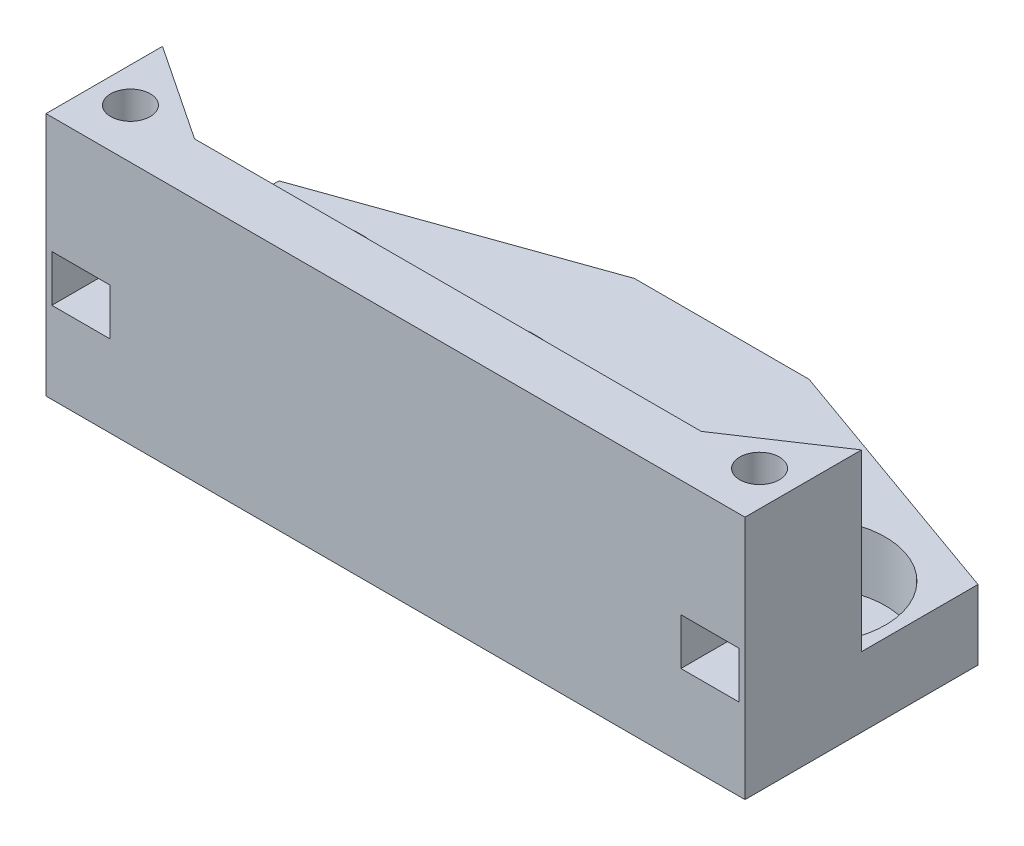
SolidWorks part; units mm, degrees
ref_plane "Front Plane" through (0, 0, 0) normal (0, 0, 1) x (1, 0, 0)
ref_plane "Top Plane" through (0, 0, 0) normal (0, 1, 0) x (1, 0, 0)
ref_plane "Right Plane" through (0, 0, 0) normal (1, 0, 0) x (0, 0, -1)
sketch "Sketch1" plane through (0, 0, 0) normal (0, 1, 0) x (1, 0, 0)
  line L0 (0, 0) -> (60, 0)
  line L1 (60, 0) -> (60, 20)
  line L2 (60, 20) -> (37.5, 28)
  line L3 (37.5, 28) -> (22.5, 28)
  line L4 (22.5, 28) -> (0, 20)
  line L5 (0, 20) -> (0, 0)
  dimension "D1" = 20
  dimension "D2" = 8
  dimension "D3" = 15
  dimension "D4" = 60
extrude "Boss-Extrude1" add sketch "Sketch1" along normal blind 6
sketch "Sketch2" plane through (0, 6, 0) normal (0, 1, 0) x (1, 0, 0)
  line L0 (6.1696, 13) -> (50006.1696, 13) construction
  line L2 (30, 21) -> (30, -49979) construction
  line L3 (37.5, 28) -> (22.5, 28) construction
  line L4 (22.5, 13) -> (37.5, 13)
  line L5 (0, 0) -> (60, 0) construction
  circle A0 centre (7.5, 13) radius 2.15
  circle A1 centre (22.5, 13) radius 2.15
  circle A2 centre (37.5, 13) radius 2.15
  circle A3 centre (52.5, 13) radius 2.15
  circle A4 centre (7.5, 13) radius 6.55
  circle A5 centre (22.5, 13) radius 6.55
  circle A6 centre (37.5, 13) radius 6.55
  circle A7 centre (52.5, 13) radius 6.55
  point P11 (30, 13)
  point P16 (30, 28)
  dimension "D1" = 15
  dimension "D2" = 15
  dimension "D3" = 15
  dimension "D4" = 4.3
  dimension "D6" = 13.1
  dimension "D5" = 13
extrude "Boss-Extrude2" [suppressed] add sketch "Sketch2" along normal blind 25 contours A0 | A1 | A2 | A3
sketch "Sketch3" plane through (0, 6, 0) normal (0, 1, 0) x (1, 0, 0)
  line L0 (0, 0) -> (15, 0)
  line L1 (0, 0) -> (60, 0) construction
  line L2 (15, 0) -> (0, 10)
  line L3 (0, 20) -> (0, 0) construction
  line L4 (0, 10) -> (0, 0)
  line L5 (60, 0) -> (60, 10)
  line L6 (60, 0) -> (60, 20) construction
  line L7 (60, 10) -> (45, 0)
  line L8 (45, 0) -> (60, 0)
  line L9 (8.25, 4.5) -> (51.75, 4.5)
  line L10 (45, 0) -> (15, 0)
  line M13 (0, 20) -> (0, 0)
  line M14 (0, 0) -> (60, 0)
  line M15 (60, 0) -> (60, 20)
  dimension "D1" = 4.5
  dimension "D2" = 10
  dimension "D3" = 15
extrude "Boss-Extrude3" add sketch "Sketch3" along normal blind 15 contours L2 M14 M13 | L9 L2 L7 M14 | L7 M15 M14 region at (5, 6, -3.3333) region at (30, 6, -2.3878) region at (55, 6, -3.3333)
sketch "Sketch4" plane through (0, 21, 0) normal (0, 1, 0) x (1, 0, 0)
  line L0 (60, 0) -> (60, 10) construction
  line L1 (0, 10) -> (0, 0) construction
  line L2 (0, 0) -> (60, 0) construction
  line L3 (22.5, 2.25) -> (37.5, 2.25) construction
  line L4 (30, 28) -> (30, 0) construction
  line L5 (37.5, 28) -> (22.5, 28) construction
  circle A0 centre (3, 4.25) radius 1.7
  circle A1 centre (57, 4.25) radius 1.7
  circle A2 centre (22.5, 2.25) radius 1.7
  circle A3 centre (37.5, 2.25) radius 1.7
  point P19 (30, 2.25)
  dimension "D1" = 3.4
  dimension "D2" = 15
  dimension "D3" = 2
  dimension "D4" = 3
  dimension "D5" = 3
  dimension "D6" = 2.25
extrude "Cut-Extrude1" cut sketch "Sketch4" against normal blind 10 contours A0 | A1 region at (3, 21, -4.25) region at (57, 21, -4.25)
sketch "Sketch6" plane through (0, 21, 0) normal (0, 1, 0) x (1, 0, 0)
  line L0 (5.5, 2.8066) -> (5.5, 0)
  line L1 (5.5, 5.6934) -> (3, 7.1368)
  line L2 (3, 7.1368) -> (0.5, 5.6934)
  line L3 (0.5, 5.6934) -> (0.5, 2.8066)
  line L4 (0.5, 2.8066) -> (3, 1.3632)
  line L5 (3, 1.3632) -> (5.5, 2.8066)
  line L6 (5.5, 2.8066) -> (5.5, 5.6934)
  line L7 (57, 7.1368) -> (54.5, 5.6934)
  line L8 (54.5, 5.6934) -> (54.5, 2.8066)
  line L9 (54.5, 2.8066) -> (57, 1.3632)
  line L10 (57, 1.3632) -> (59.5, 2.8066)
  line L11 (59.5, 2.8066) -> (59.5, 5.6934)
  line L12 (59.5, 5.6934) -> (57, 7.1368)
  line L13 (0, 0) -> (60, 0) construction
  line L14 (0.5, 2.8066) -> (0.5, 0)
  line L15 (0.5, 0) -> (5.5, 0)
  line L16 (59.5, 2.8066) -> (59.5, 0)
  line L17 (59.5, 0) -> (54.5, 0)
  line L18 (54.5, 0) -> (54.5, 2.8066)
  circle A0 centre (3, 4.25) radius 2.5 construction
  circle A1 centre (57, 4.25) radius 2.5 construction
  circle M17 centre (57, 4.25) radius 1.7
  line M18 (0, 0) -> (60, 0)
  dimension "D1" = 5
extrude "Cut-Extrude2" cut sketch "Sketch6" against normal blind 4 from offset 10 contours L4 L14 L0 L5 M18 | L18 L16 L10 L9 M18 | L11 L12 L7 L8 L9 L10 M17 | M17 | L1 L2 L3 L4 L5 L6 region at (57, 21, -1.0841) region at (3, 21, -1.0841) region at (54.5764, 21, -4.25) region at (57, 21, -4.25) offset against normal yes
extrude "Cut-Extrude3" cut sketch "Sketch2<4>" against normal blind 5.1 contours A4 A0 | A5 A1 | A6 A2 | A3 | A7 A3 | A2 | A1 | A0 region at (16.1353, 6, -13) region at (37.5, 6, -15.0892) region at (37.5, 6, -19.3647) region at (20.4108, 6, -13) region at (7.5, 6, -13) region at (52.5, 6, -13) region at (1.1353, 6, -13) region at (46.1353, 6, -13)
sketch "Sketch2<4>" plane through (0, 6, 0) normal (0, 1, 0) x (1, 0, 0) same geometry as "Sketch2"
extrude "Cut-Extrude4" cut sketch "Sketch2<5>" against normal through all contours A0 | A1 | A2 | A3 region at (37.5, 6, -15.0892) region at (20.4108, 6, -13) region at (7.5, 6, -13) region at (52.5, 6, -13)
sketch "Sketch2<5>" plane through (0, 6, 0) normal (0, 1, 0) x (1, 0, 0) same geometry as "Sketch2"
